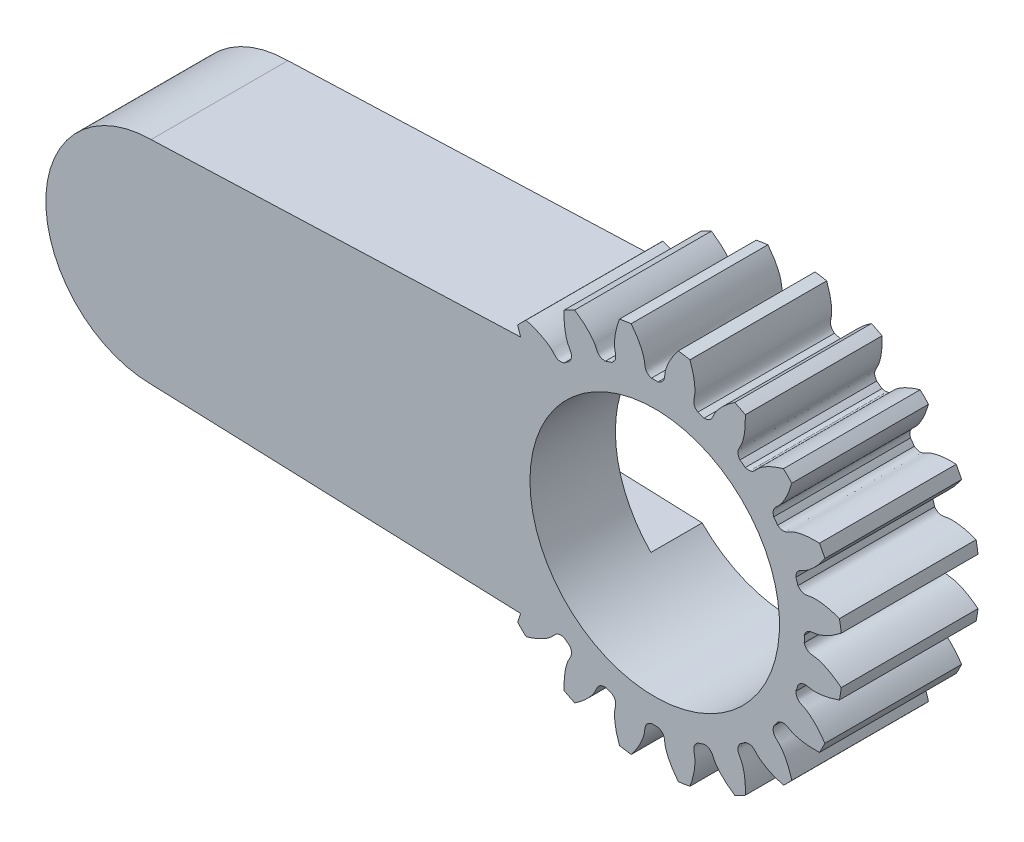
SolidWorks part; units mm, degrees
ref_plane "前视基准面" through (0, 0, 0) normal (0, 0, 1) x (1, 0, 0)
ref_plane "上视基准面" through (0, 0, 0) normal (0, 1, 0) x (1, 0, 0)
ref_plane "右视基准面" through (0, 0, 0) normal (1, 0, 0) x (0, 0, -1)
other "Configuration Table"
sketch "草图1" plane through (0, 0, 0) normal (0, 0, 1) x (1, 0, 0)
  circle A0 centre (0, 0) radius 5.5
extrude "凸台-拉伸1" add sketch "草图1" along normal blind 4
ref_axis "基准轴1" through (0, 0, 4) along (0, 0, -1)
sketch "草图2" plane through (0, 0, 0) normal (0, 0, 1) x (1, 0, 0)
  line L0 (0, 0) -> (0, 5.5) construction
  circle A0 centre (0, 0) radius 5.5 construction
  arc A1 (0.0967, 4.3739) -> (-0.0967, 4.3739) centre (0, 0) ccw
  arc A2 (1.5906, 6.2491) -> (-1.5906, 6.2491) centre (0, 0) ccw
  spline S0 degree 3 poles (0.0967, 4.3739) (0.3056, 4.4467) (0.2785, 4.5936) (0.3064, 4.735) (0.3094, 4.7488) (0.3132, 4.7643) (0.3176, 4.7816) (0.323, 4.8006) (0.3293, 4.8213) (0.3365, 4.8436) (0.3448, 4.8676) (0.3543, 4.8932) (0.3649, 4.9203) (0.3768, 4.9489) (0.3901, 4.979) (0.4047, 5.0106) (0.4208, 5.0435) (0.4383, 5.0778) (0.4575, 5.1134) (0.4783, 5.1502) (0.5008, 5.1882) (0.525, 5.2274) (0.551, 5.2676) (0.5789, 5.3089) (0.6087, 5.3511) (0.6404, 5.3943) (0.6741, 5.4383) (0.7099, 5.4831) (0.7477, 5.5286) (0.7877, 5.5748) (0.8299, 5.6215) (0.8743, 5.6688) (0.9209, 5.7165) (0.9698, 5.7646) (1.0211, 5.813) (1.0747, 5.8617) (1.1306, 5.9104) (1.189, 5.9593) (1.2498, 6.0082) (1.313, 6.057) (1.3788, 6.1056) (1.4707, 6.1708) (1.542, 6.2182) (1.5906, 6.2491) knots 0 0 0 0 0.165916 0.170906 0.176664 0.183189 0.190482 0.198542 0.207371 0.216967 0.22733 0.238462 0.250361 0.263027 0.276462 0.290664 0.305634 0.321371 0.337876 0.355149 0.37319 0.391998 0.411574 0.431917 0.453028 0.474907 0.497554 0.520968 0.54515 0.570099 0.595817 0.622302 0.649554 0.677575 0.706363 0.735918 0.766242 0.797333 0.829191 0.861818 0.895212 0.929373 1 1 1 1
  spline S1 degree 3 poles (-0.0967, 4.3739) (-0.3056, 4.4467) (-0.2785, 4.5936) (-0.3064, 4.735) (-0.3094, 4.7488) (-0.3132, 4.7643) (-0.3176, 4.7816) (-0.323, 4.8006) (-0.3293, 4.8213) (-0.3365, 4.8436) (-0.3448, 4.8676) (-0.3543, 4.8932) (-0.3649, 4.9203) (-0.3768, 4.9489) (-0.3901, 4.979) (-0.4047, 5.0106) (-0.4208, 5.0435) (-0.4383, 5.0778) (-0.4575, 5.1134) (-0.4783, 5.1502) (-0.5008, 5.1882) (-0.525, 5.2274) (-0.551, 5.2676) (-0.5789, 5.3089) (-0.6087, 5.3511) (-0.6404, 5.3943) (-0.6741, 5.4383) (-0.7099, 5.4831) (-0.7477, 5.5286) (-0.7877, 5.5748) (-0.8299, 5.6215) (-0.8743, 5.6688) (-0.9209, 5.7165) (-0.9698, 5.7646) (-1.0211, 5.813) (-1.0747, 5.8617) (-1.1306, 5.9104) (-1.189, 5.9593) (-1.2498, 6.0082) (-1.313, 6.057) (-1.3788, 6.1056) (-1.4707, 6.1708) (-1.542, 6.2182) (-1.5906, 6.2491) knots 0 0 0 0 0.165916 0.170906 0.176664 0.183189 0.190482 0.198542 0.207371 0.216967 0.22733 0.238462 0.250361 0.263027 0.276462 0.290664 0.305634 0.321371 0.337876 0.355149 0.37319 0.391998 0.411574 0.431917 0.453028 0.474907 0.497554 0.520968 0.54515 0.570099 0.595817 0.622302 0.649554 0.677575 0.706363 0.735918 0.766242 0.797333 0.829191 0.861818 0.895212 0.929373 1 1 1 1
extrude "切除-拉伸1" cut sketch "草图2" along normal through all
pattern_circular "阵列(圆周)1" count 20 over 360 about axis through (0, 0, 4) along (0, 0, -1) of "切除-拉伸1"
sketch "草图3" plane through (0, 0, 0) normal (0, 0, 1) x (1, 0, 0)
  circle A0 centre (0, 0) radius 5 construction
  dimension "Dn" = 10
sketch "草图4" plane through (0, 0, 0) normal (0, 0, -1) x (-1, 0, 0)
  circle A0 centre (0, 0) radius 3.65
  dimension "D1" = 7.3
extrude "切除-拉伸2" cut sketch "草图4" against normal through all
sketch "草图5" plane through (0, 0, 0) normal (0, 0, -1) x (-1, 0, 0)
  line L2 (0, 0) -> (18.889, 0) construction
  line L5 (2.6115, -2.55) -> (14.7115, -2.1)
  line L6 (2.6115, 2.55) -> (2.6115, -2.55)
  line L7 (2.6115, 2.55) -> (14.7115, 2.1)
  line L8 (14.7115, -2.1) -> (14.7115, 2.1) construction
  arc A2 (14.7115, 2.1) -> (14.7115, -2.1) centre (14.7115, 0) cw
  circle A3 centre (0, 0) radius 3.65 construction
  dimension "D1" = 2.1
  dimension "D2" = 12.1
  dimension "D3" = 5.1
extrude "拉伸-薄壁4" add sketch "草图5" against normal blind 1.5 thin thin type one direction wall 1
sketch "草图6" plane through (0, 0, 0) normal (0, 0, -1) x (-1, 0, 0)
  line L0 (2.6115, 2.55) -> (5.9363, 2.4264)
  line L1 (14.7115, 2.1) -> (4.9171, 2.4643) construction
  line L2 (2.6115, -2.55) -> (5.9363, -2.4264)
  line L3 (2.6115, 2.55) -> (2.6115, -2.55) construction
  line L4 (4.9171, -2.4643) -> (14.7115, -2.1) construction
  line L5 (5.9363, -2.4264) -> (5.9363, 2.4264)
  line L6 (1.6115, -3.275) -> (1.6115, 3.275)
  arc A0 (1.6115, -3.275) -> (2.6115, -2.55) centre (0, 0) ccw
  arc A1 (2.6115, -2.55) -> (2.6115, 2.55) centre (0, 0) ccw construction
  arc A2 (2.6115, 2.55) -> (1.6115, 3.275) centre (0, 0) ccw
extrude "切除-拉伸3" cut sketch "草图6" against normal blind 1.5
sketch "草图7" plane through (0, 0, 0) normal (0, 0, -1) x (-1, 0, 0)
  line L0 (3.9221, -3.5019) -> (14.7319, -3.0999) construction
  line L1 (14.7319, 3.0999) -> (3.9221, 3.5019) construction
  line L2 (3.9221, -3.5019) -> (14.7319, -3.0999)
  line L3 (14.7319, 3.0999) -> (3.9221, 3.5019)
  line L4 (3.9221, 3.5019) -> (2.6115, 2.55)
  line L5 (3.9221, -3.5019) -> (2.6115, -2.55)
  arc A0 (2.6115, -2.55) -> (2.6115, 2.55) centre (0, 0) ccw
  arc A1 (14.7319, -3.0999) -> (14.7319, 3.0999) centre (14.7115, 0) ccw construction
  arc A2 (14.7319, -3.0999) -> (14.7319, 3.0999) centre (14.7115, 0) ccw
  arc A3 (2.6115, 2.55) -> (2.6115, -2.55) centre (0, 0) ccw construction
extrude "凸台-拉伸3" add sketch "草图7" against normal up to surface (4 mm away) from surface up to face at (-3.65, 0, 4) starting at face at (-7.0874, -0.0439, 1.5)
